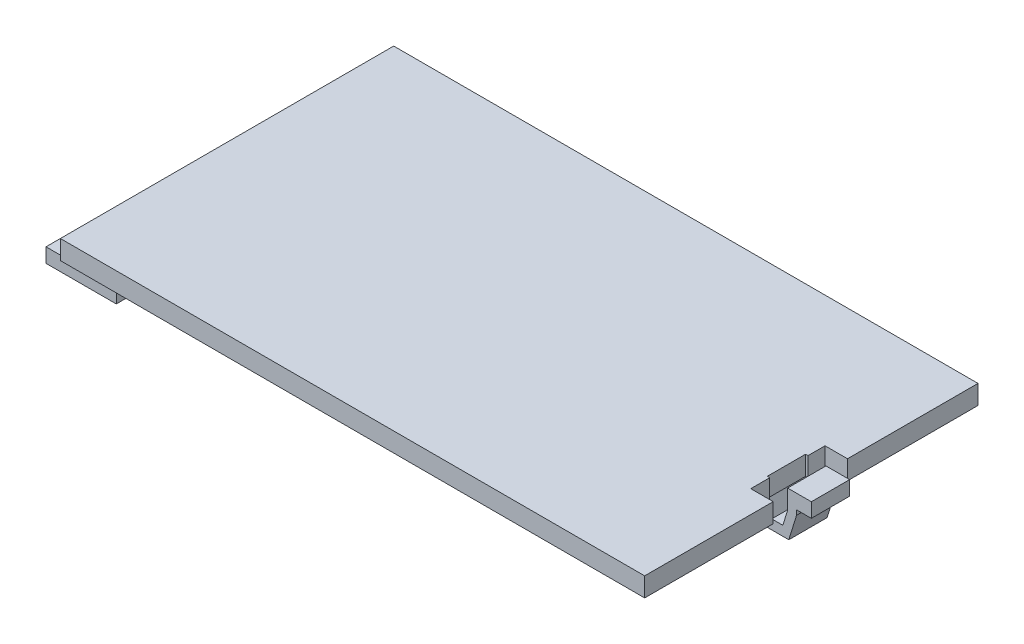
SolidWorks part; units mm, degrees
ref_plane "前视基准面" through (0, 0, 0) normal (0, 0, 1) x (1, 0, 0)
ref_plane "上视基准面" through (0, 0, 0) normal (0, 1, 0) x (1, 0, 0)
ref_plane "右视基准面" through (0, 0, 0) normal (1, 0, 0) x (0, 0, -1)
sketch "草图1" plane through (0, 0, 0) normal (0, 1, 0) x (1, 0, 0)
  line L1 (0, 0) -> (61, 0)
  line L2 (0, 0) -> (0, 34.8)
  line L3 (0, 34.8) -> (61, 34.8)
  line L4 (61, 0) -> (61, 34.8)
  dimension "D1" = 34.8
  dimension "D2" = 61
extrude "凸台-拉伸1" add sketch "草图1" along normal blind 2
sketch "草图2" plane through (0, 0, 0) normal (0, -1, 0) x (1, 0, 0)
  line L0 (0, -17.4) -> (74.8791, -17.4) construction
  line L1 (5.3381, -0.5) -> (-2, -0.5)
  line L2 (5.3381, -0.5) -> (5.3381, -2.5)
  line L3 (5.3381, -2.5) -> (-2, -2.5)
  line L4 (-2, -0.5) -> (-2, -2.5)
  line L5 (0, -34.8) -> (0, 0) construction
  line L10 (5.3381, -32.3) -> (-2, -32.3)
  line L11 (-2, -34.3) -> (-2, -32.3)
  line L12 (5.3381, -34.3) -> (-2, -34.3)
  line L13 (5.3381, -34.3) -> (5.3381, -32.3)
  line L14 (0, 0) -> (61, 0) construction
  point P13 (0, 0)
  dimension "D1" = 2
  dimension "D2" = 2
  dimension "D3" = 0.5
extrude "凸台-拉伸2" add sketch "草图2" along normal blind 1.5
sketch "草图3" plane through (0, 2, 0) normal (0, 1, 0) x (1, 0, 0)
  line L0 (0, 17.4) -> (71.509, 17.4) construction
  line L1 (0, 34.8) -> (0, 0) construction
  line L2 (61, 0) -> (61, 34.8) construction
  line L3 (61, 19.4) -> (63, 19.4)
  line L4 (61, 19.4) -> (61, 15.4)
  line L5 (61, 15.4) -> (63, 15.4)
  line L6 (63, 19.4) -> (63, 15.4)
  line L7 (61, 19.4) -> (63, 15.4) construction
  point P10 (62, 17.4)
  point P11 (0, 0)
  dimension "D1" = 4
  dimension "D2" = 2
extrude "凸台-拉伸3" add sketch "草图3" against normal blind 1.5
sketch "草图5" plane through (0, 0, -15.4) normal (0, 0, 1) x (1, 0, 0)
  line L1 (61, 2) -> (61, 0) construction
  line L3 (59.5714, -2.616) -> (58.3104, -2.616)
  line L4 (58.3104, -2.616) -> (57.552, 0)
  line L5 (0, 0) -> (61, 0) construction
  line L6 (57.552, 0) -> (57.552, 2)
  line L7 (0, 2) -> (61, 2) construction
  line L8 (57.552, 2) -> (61, 2)
  line L9 (61, 0.5) -> (61, 2) construction
  line L11 (61, 2) -> (61.4556, 2)
  line L12 (61, 2) -> (63, 2) construction
  line L13 (61.4556, 2) -> (61.4556, 0)
  line L14 (61.4556, 0) -> (60.6464, -2.616)
  line L15 (60.6464, -2.616) -> (59.5714, -2.616)
  point P0 (0, 0)
extrude "凸台-拉伸4" add sketch "草图5" against normal blind 4
sketch "草图6" plane through (0, 0, -15.4) normal (0, 0, 1) x (1, 0, 0)
  line L0 (58.4013, 0) -> (58.8698, -1.616)
  line L1 (0, 0) -> (61, 0) construction
  line L2 (58.8698, -1.616) -> (60.0269, -1.616)
  line L3 (60.0269, -1.616) -> (60.5268, 0)
  line L4 (60.5268, 0) -> (60.5268, 2)
  line L5 (0, 2) -> (61, 2) construction
  line L6 (60.5268, 2) -> (58.4013, 2)
  line L7 (58.4013, 2) -> (58.4013, 0)
  line L8 (58.3104, -2.616) -> (60.6464, -2.616) construction
  line L9 (57.552, 0) -> (58.3104, -2.616) construction
  line L10 (60.6464, -2.616) -> (61.4556, 0) construction
  dimension "D1" = 1
extrude "切除-拉伸1" cut sketch "草图6" against normal blind 4
sketch "草图7" plane through (0, 2, 0) normal (0, 1, 0) x (1, 0, 0)
  line L0 (61, 0) -> (61, 15.4) construction
  line L1 (58.6565, 21.1734) -> (61, 21.1734)
  line L2 (58.6565, 21.1734) -> (58.6565, 13.4188)
  line L3 (58.6565, 13.4188) -> (61, 13.4188)
  line L5 (61, 21.1734) -> (61, 19.4)
  line L6 (61, 19.4) -> (60.5268, 19.4)
  line L7 (60.5268, 19.4) -> (60.5268, 15.4)
  line L8 (60.5268, 15.4) -> (61, 15.4)
  line L9 (61, 15.4) -> (63, 15.4) construction
  line L10 (61, 15.4) -> (61, 13.4188)
extrude "切除-拉伸2" cut sketch "草图7" against normal blind 2
